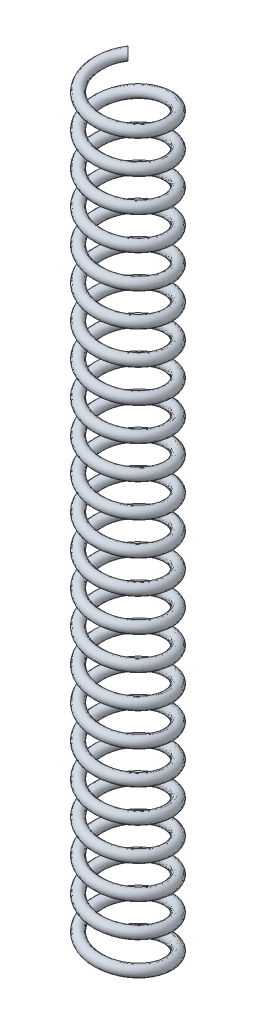
SolidWorks part; units mm, degrees
note: '?' marks a value the reader was unsure of.
ref_plane "Front Plane" through (0, 0, 0) normal (0, 0, 1) x (1, 0, 0)
ref_plane "Top Plane" through (0, 0, 0) normal (0, 1, 0) x (1, 0, 0)
ref_plane "Right Plane" through (0, 0, 0) normal (1, 0, 0) x (0, 0, -1)
sketch "Sketch1" plane through (0, 0, 0) normal (0, 1, 0) x (1, 0, 0)
  circle A0 centre (0, 0) radius 2.325
  dimension "D1" = 4.65
curve "Helix/Spiral1" pitch 2.1739 height 50 radius 2.325 left hand yes centre (0, 0, 0) axis (0, 1, 0) start towards (0, 0, 1)
ref_axis "Axis1" through (0, 52.5, 0) along (0, -1, 0)?
ref_plane "Plane1" through (0, 0, 0) normal (0.7071, 0, -0.7071) x (-0.7071, 0, -0.7071)
sketch "Sketch2" plane through (0, 0, 0) normal (0.7071, 0, -0.7071) x (-0.7071, 0, -0.7071)
  circle A0 centre (2.325, 50) radius 0.35
  spline S0 degree 3 poles (-1990.5635, 164.9826) (-222.6093, -6.3743) (13.3243, -2.7822) (1.6868, 0.2717) (0.9129, 0.4076) (0, 0.5435) (-0.9129, 0.6793) (-1.6868, 0.8152) (-2.2039, 0.9511) (-2.3855, 1.087) (-2.2039, 1.2228) (-1.6868, 1.3587) (-0.6549, 1.5399) (0.6549, 1.721) (1.6868, 1.9022) (2.2039, 2.038) (2.3855, 2.1739) (2.2039, 2.3098) (1.6868, 2.4457) (0.6549, 2.6268) (-0.6549, 2.808) (-1.6868, 2.9891) (-2.2039, 3.125) (-2.3855, 3.2609) (-2.2039, 3.3967) (-1.6868, 3.5326) (-0.6549, 3.7138) (0.6549, 3.8949) (1.6868, 4.0761) (2.2039, 4.212) (2.3855, 4.3478) (2.2039, 4.4837) (1.6868, 4.6196) (0.6549, 4.8007) (-0.6549, 4.9819) (-1.6868, 5.163) (-2.2039, 5.2989) (-2.3855, 5.4348) (-2.2039, 5.5707) (-1.6868, 5.7065) (-0.6549, 5.8877) (0.6549, 6.0688) (1.6868, 6.25) (2.2039, 6.3859) (2.3855, 6.5217) (2.2039, 6.6576) (1.6868, 6.7935) (0.6549, 6.9746) (-0.6549, 7.1558) (-1.6868, 7.337) (-2.2039, 7.4728) (-2.3855, 7.6087) (-2.2039, 7.7446) (-1.6868, 7.8804) (-0.6549, 8.0616) (0.6549, 8.2428) (1.6868, 8.4239) (2.2039, 8.5598) (2.3855, 8.6957) (2.2039, 8.8315) (1.6868, 8.9674) (0.6549, 9.1486) (-0.6549, 9.3297) (-1.6868, 9.5109) (-2.2039, 9.6467) (-2.3855, 9.7826) (-2.2039, 9.9185) (-1.6868, 10.0543) (-0.6549, 10.2355) (0.6549, 10.4167) (1.6868, 10.5978) (2.2039, 10.7337) (2.3855, 10.8696) (2.2039, 11.0054) (1.6868, 11.1413) (0.6549, 11.3225) (-0.6549, 11.5036) (-1.6868, 11.6848) (-2.2039, 11.8207) (-2.3855, 11.9565) (-2.2039, 12.0924) (-1.6868, 12.2283) (-0.6549, 12.4094) (0.6549, 12.5906) (1.6868, 12.7717) (2.2039, 12.9076) (2.3855, 13.0435) (2.2039, 13.1793) (1.6868, 13.3152) (0.6549, 13.4964) (-0.6549, 13.6775) (-1.6868, 13.8587) (-2.2039, 13.9946) (-2.3855, 14.1304) (-2.2039, 14.2663) (-1.6868, 14.4022) (-0.6549, 14.5833) (0.6549, 14.7645) (1.6868, 14.9457) (2.2039, 15.0815) (2.3855, 15.2174) (2.2039, 15.3533) (1.6868, 15.4891) (0.6549, 15.6703) (-0.6549, 15.8514) (-1.6868, 16.0326) (-2.2039, 16.1685) (-2.3855, 16.3043) (-2.2039, 16.4402) (-1.6868, 16.5761) (-0.6549, 16.7572) (0.6549, 16.9384) (1.6868, 17.1196) (2.2039, 17.2554) (2.3855, 17.3913) (2.2039, 17.5272) (1.6868, 17.663) (0.6549, 17.8442) (-0.6549, 18.0254) (-1.6868, 18.2065) (-2.2039, 18.3424) (-2.3855, 18.4783) (-2.2039, 18.6141) (-1.6868, 18.75) (-0.6549, 18.9312) (0.6549, 19.1123) (1.6868, 19.2935) (2.2039, 19.4293) (2.3855, 19.5652) (2.2039, 19.7011) (1.6868, 19.837) (0.6549, 20.0181) (-0.6549, 20.1993) (-1.6868, 20.3804) (-2.2039, 20.5163) (-2.3855, 20.6522) (-2.2039, 20.788) (-1.6868, 20.9239) (-0.6549, 21.1051) (0.6549, 21.2862) (1.6868, 21.4674) (2.2039, 21.6033) (2.3855, 21.7391) (2.2039, 21.875) (1.6868, 22.0109) (0.6549, 22.192) (-0.6549, 22.3732) (-1.6868, 22.5543) (-2.2039, 22.6902) (-2.3855, 22.8261) (-2.2039, 22.962) (-1.6868, 23.0978) (-0.6549, 23.279) (0.6549, 23.4601) (1.6868, 23.6413) (2.2039, 23.7772) (2.3855, 23.913) (2.2039, 24.0489) (1.6868, 24.1848) (0.6549, 24.3659) (-0.6549, 24.5471) (-1.6868, 24.7283) (-2.2039, 24.8641) (-2.3855, 25) (-2.2039, 25.1359) (-1.6868, 25.2717) (-0.6549, 25.4529) (0.6549, 25.6341) (1.6868, 25.8152) (2.2039, 25.9511) (2.3855, 26.087) (2.2039, 26.2228) (1.6868, 26.3587) (0.6549, 26.5399) (-0.6549, 26.721) (-1.6868, 26.9022) (-2.2039, 27.038) (-2.3855, 27.1739) (-2.2039, 27.3098) (-1.6868, 27.4457) (-0.6549, 27.6268) (0.6549, 27.808) (1.6868, 27.9891) (2.2039, 28.125) (2.3855, 28.2609) (2.2039, 28.3967) (1.6868, 28.5326) (0.6549, 28.7138) (-0.6549, 28.8949) (-1.6868, 29.0761) (-2.2039, 29.212) (-2.3855, 29.3478) (-2.2039, 29.4837) (-1.6868, 29.6196) (-0.6549, 29.8007) (0.6549, 29.9819) (1.6868, 30.163) (2.2039, 30.2989) (2.3855, 30.4348) (2.2039, 30.5707) (1.6868, 30.7065) (0.6549, 30.8877) (-0.6549, 31.0688) (-1.6868, 31.25) (-2.2039, 31.3859) (-2.3855, 31.5217) (-2.2039, 31.6576) (-1.6868, 31.7935) (-0.6549, 31.9746) (0.6549, 32.1558) (1.6868, 32.337) (2.2039, 32.4728) (2.3855, 32.6087) (2.2039, 32.7446) (1.6868, 32.8804) (0.6549, 33.0616) (-0.6549, 33.2428) (-1.6868, 33.4239) (-2.2039, 33.5598) (-2.3855, 33.6957) (-2.2039, 33.8315) (-1.6868, 33.9674) (-0.6549, 34.1486) (0.6549, 34.3297) (1.6868, 34.5109) (2.2039, 34.6467) (2.3855, 34.7826) (2.2039, 34.9185) (1.6868, 35.0543) (0.6549, 35.2355) (-0.6549, 35.4167) (-1.6868, 35.5978) (-2.2039, 35.7337) (-2.3855, 35.8696) (-2.2039, 36.0054) (-1.6868, 36.1413) (-0.6549, 36.3225) (0.6549, 36.5036) (1.6868, 36.6848) (2.2039, 36.8207) (2.3855, 36.9565) (2.2039, 37.0924) (1.6868, 37.2283) (0.6549, 37.4094) (-0.6549, 37.5906) (-1.6868, 37.7717) (-2.2039, 37.9076) (-2.3855, 38.0435) (-2.2039, 38.1793) (-1.6868, 38.3152) (-0.6549, 38.4964) (0.6549, 38.6775) (1.6868, 38.8587) (2.2039, 38.9946) (2.3855, 39.1304) (2.2039, 39.2663) (1.6868, 39.4022) (0.6549, 39.5833) (-0.6549, 39.7645) (-1.6868, 39.9457) (-2.2039, 40.0815) (-2.3855, 40.2174) (-2.2039, 40.3533) (-1.6868, 40.4891) (-0.6549, 40.6703) (0.6549, 40.8514) (1.6868, 41.0326) (2.2039, 41.1685) (2.3855, 41.3043) (2.2039, 41.4402) (1.6868, 41.5761) (0.6549, 41.7572) (-0.6549, 41.9384) (-1.6868, 42.1196) (-2.2039, 42.2554) (-2.3855, 42.3913) (-2.2039, 42.5272) (-1.6868, 42.663) (-0.6549, 42.8442) (0.6549, 43.0254) (1.6868, 43.2065) (2.2039, 43.3424) (2.3855, 43.4783) (2.2039, 43.6141) (1.6868, 43.75) (0.6549, 43.9312) (-0.6549, 44.1123) (-1.6868, 44.2935) (-2.2039, 44.4293) (-2.3855, 44.5652) (-2.2039, 44.7011) (-1.6868, 44.837) (-0.6549, 45.0181) (0.6549, 45.1993) (1.6868, 45.3804) (2.2039, 45.5163) (2.3855, 45.6522) (2.2039, 45.788) (1.6868, 45.9239) (0.6549, 46.1051) (-0.6549, 46.2862) (-1.6868, 46.4674) (-2.2039, 46.6033) (-2.3855, 46.7391) (-2.2039, 46.875) (-1.6868, 47.0109) (-0.6549, 47.192) (0.6549, 47.3732) (1.6868, 47.5543) (2.2039, 47.6902) (2.3855, 47.8261) (2.2039, 47.962) (1.6868, 48.0978) (0.6549, 48.279) (-0.6549, 48.4601) (-1.6868, 48.6413) (-2.2039, 48.7772) (-2.3855, 48.913) (-2.2039, 49.0489) (-1.6868, 49.1848) (-0.9129, 49.3207) (0, 49.4565) (0.9129, 49.5924) (1.6868, 49.7283) (13.324, 52.7821) (-222.5989, 56.3741) (-1990.4449, -114.9711) knots -0.175308 -0.175308 -0.175308 -0.175308 0.002717 0.005435 0.008152 0.01087 0.013587 0.016304 0.019022 0.021739 0.024457 0.027174 0.029891 0.035326 0.038043 0.040761 0.043478 0.046196 0.048913 0.05163 0.057065 0.059783 0.0625 0.065217 0.067935 0.070652 0.07337 0.078804 0.081522 0.084239 0.086957 0.089674 0.092391 0.095109 0.100543 0.103261 0.105978 0.108696 0.111413 0.11413 0.116848 0.122283 0.125 0.127717 0.130435 0.133152 0.13587 0.138587 0.144022 0.146739 0.149457 0.152174 0.154891 0.157609 0.160326 0.165761 0.168478 0.171196 0.173913 0.17663 0.179348 0.182065 0.1875 0.190217 0.192935 0.195652 0.19837 0.201087 0.203804 0.209239 0.211957 0.214674 0.217391 0.220109 0.222826 0.225543 0.230978 0.233696 0.236413 0.23913 0.241848 0.244565 0.247283 0.252717 0.255435 0.258152 0.26087 0.263587 0.266304 0.269022 0.274457 0.277174 0.279891 0.282609 0.285326 0.288043 0.290761 0.296196 0.298913 0.30163 0.304348 0.307065 0.309783 0.3125 0.317935 0.320652 0.32337 0.326087 0.328804 0.331522 0.334239 0.339674 0.342391 0.345109 0.347826 0.350543 0.353261 0.355978 0.361413 0.36413 0.366848 0.369565 0.372283 0.375 0.377717 0.383152 0.38587 0.388587 0.391304 0.394022 0.396739 0.399457 0.404891 0.407609 0.410326 0.413043 0.415761 0.418478 0.421196 0.42663 0.429348 0.432065 0.434783 0.4375 0.440217 0.442935 0.44837 0.451087 0.453804 0.456522 0.459239 0.461957 0.464674 0.470109 0.472826 0.475543 0.478261 0.480978 0.483696 0.486413 0.491848 0.494565 0.497283 0.5 0.502717 0.505435 0.508152 0.513587 0.516304 0.519022 0.521739 0.524457 0.527174 0.529891 0.535326 0.538043 0.540761 0.543478 0.546196 0.548913 0.55163 0.557065 0.559783 0.5625 0.565217 0.567935 0.570652 0.57337 0.578804 0.581522 0.584239 0.586957 0.589674 0.592391 0.595109 0.600543 0.603261 0.605978 0.608696 0.611413 0.61413 0.616848 0.622283 0.625 0.627717 0.630435 0.633152 0.63587 0.638587 0.644022 0.646739 0.649457 0.652174 0.654891 0.657609 0.660326 0.665761 0.668478 0.671196 0.673913 0.67663 0.679348 0.682065 0.6875 0.690217 0.692935 0.695652 0.69837 0.701087 0.703804 0.709239 0.711957 0.714674 0.717391 0.720109 0.722826 0.725543 0.730978 0.733696 0.736413 0.73913 0.741848 0.744565 0.747283 0.752717 0.755435 0.758152 0.76087 0.763587 0.766304 0.769022 0.774457 0.777174 0.779891 0.782609 0.785326 0.788043 0.790761 0.796196 0.798913 0.80163 0.804348 0.807065 0.809783 0.8125 0.817935 0.820652 0.82337 0.826087 0.828804 0.831522 0.834239 0.839674 0.842391 0.845109 0.847826 0.850543 0.853261 0.855978 0.861413 0.86413 0.866848 0.869565 0.872283 0.875 0.877717 0.883152 0.88587 0.888587 0.891304 0.894022 0.896739 0.899457 0.904891 0.907609 0.910326 0.913043 0.915761 0.918478 0.921196 0.92663 0.929348 0.932065 0.934783 0.9375 0.940217 0.942935 0.94837 0.951087 0.953804 0.956522 0.959239 0.961957 0.964674 0.970109 0.972826 0.975543 0.978261 0.980978 0.983696 0.986413 0.98913 0.991848 0.994565 0.997283 1.175304 1.175304 1.175304 1.175304 only from (2.325, 0) to (2.325, 50) construction
  spline S1 degree 3 poles (2.325, 0) (2.325, 0.045) (2.2039, 0.136) (1.6868, 0.2717) (0.9129, 0.4076) (0, 0.5435) (-0.9129, 0.6793) (-1.6868, 0.8152) (-2.2039, 0.9511) (-2.3855, 1.087) (-2.2039, 1.2228) (-1.6868, 1.3587) (-0.6549, 1.5399) (0.6549, 1.721) (1.6868, 1.9022) (2.2039, 2.038) (2.3855, 2.1739) (2.2039, 2.3098) (1.6868, 2.4457) (0.6549, 2.6268) (-0.6549, 2.808) (-1.6868, 2.9891) (-2.2039, 3.125) (-2.3855, 3.2609) (-2.2039, 3.3967) (-1.6868, 3.5326) (-0.6549, 3.7138) (0.6549, 3.8949) (1.6868, 4.0761) (2.2039, 4.212) (2.3855, 4.3478) (2.2039, 4.4837) (1.6868, 4.6196) (0.6549, 4.8007) (-0.6549, 4.9819) (-1.6868, 5.163) (-2.2039, 5.2989) (-2.3855, 5.4348) (-2.2039, 5.5707) (-1.6868, 5.7065) (-0.6549, 5.8877) (0.6549, 6.0688) (1.6868, 6.25) (2.2039, 6.3859) (2.3855, 6.5217) (2.2039, 6.6576) (1.6868, 6.7935) (0.6549, 6.9746) (-0.6549, 7.1558) (-1.6868, 7.337) (-2.2039, 7.4728) (-2.3855, 7.6087) (-2.2039, 7.7446) (-1.6868, 7.8804) (-0.6549, 8.0616) (0.6549, 8.2428) (1.6868, 8.4239) (2.2039, 8.5598) (2.3855, 8.6957) (2.2039, 8.8315) (1.6868, 8.9674) (0.6549, 9.1486) (-0.6549, 9.3297) (-1.6868, 9.5109) (-2.2039, 9.6467) (-2.3855, 9.7826) (-2.2039, 9.9185) (-1.6868, 10.0543) (-0.6549, 10.2355) (0.6549, 10.4167) (1.6868, 10.5978) (2.2039, 10.7337) (2.3855, 10.8696) (2.2039, 11.0054) (1.6868, 11.1413) (0.6549, 11.3225) (-0.6549, 11.5036) (-1.6868, 11.6848) (-2.2039, 11.8207) (-2.3855, 11.9565) (-2.2039, 12.0924) (-1.6868, 12.2283) (-0.6549, 12.4094) (0.6549, 12.5906) (1.6868, 12.7717) (2.2039, 12.9076) (2.3855, 13.0435) (2.2039, 13.1793) (1.6868, 13.3152) (0.6549, 13.4964) (-0.6549, 13.6775) (-1.6868, 13.8587) (-2.2039, 13.9946) (-2.3855, 14.1304) (-2.2039, 14.2663) (-1.6868, 14.4022) (-0.6549, 14.5833) (0.6549, 14.7645) (1.6868, 14.9457) (2.2039, 15.0815) (2.3855, 15.2174) (2.2039, 15.3533) (1.6868, 15.4891) (0.6549, 15.6703) (-0.6549, 15.8514) (-1.6868, 16.0326) (-2.2039, 16.1685) (-2.3855, 16.3043) (-2.2039, 16.4402) (-1.6868, 16.5761) (-0.6549, 16.7572) (0.6549, 16.9384) (1.6868, 17.1196) (2.2039, 17.2554) (2.3855, 17.3913) (2.2039, 17.5272) (1.6868, 17.663) (0.6549, 17.8442) (-0.6549, 18.0254) (-1.6868, 18.2065) (-2.2039, 18.3424) (-2.3855, 18.4783) (-2.2039, 18.6141) (-1.6868, 18.75) (-0.6549, 18.9312) (0.6549, 19.1123) (1.6868, 19.2935) (2.2039, 19.4293) (2.3855, 19.5652) (2.2039, 19.7011) (1.6868, 19.837) (0.6549, 20.0181) (-0.6549, 20.1993) (-1.6868, 20.3804) (-2.2039, 20.5163) (-2.3855, 20.6522) (-2.2039, 20.788) (-1.6868, 20.9239) (-0.6549, 21.1051) (0.6549, 21.2862) (1.6868, 21.4674) (2.2039, 21.6033) (2.3855, 21.7391) (2.2039, 21.875) (1.6868, 22.0109) (0.6549, 22.192) (-0.6549, 22.3732) (-1.6868, 22.5543) (-2.2039, 22.6902) (-2.3855, 22.8261) (-2.2039, 22.962) (-1.6868, 23.0978) (-0.6549, 23.279) (0.6549, 23.4601) (1.6868, 23.6413) (2.2039, 23.7772) (2.3855, 23.913) (2.2039, 24.0489) (1.6868, 24.1848) (0.6549, 24.3659) (-0.6549, 24.5471) (-1.6868, 24.7283) (-2.2039, 24.8641) (-2.3855, 25) (-2.2039, 25.1359) (-1.6868, 25.2717) (-0.6549, 25.4529) (0.6549, 25.6341) (1.6868, 25.8152) (2.2039, 25.9511) (2.3855, 26.087) (2.2039, 26.2228) (1.6868, 26.3587) (0.6549, 26.5399) (-0.6549, 26.721) (-1.6868, 26.9022) (-2.2039, 27.038) (-2.3855, 27.1739) (-2.2039, 27.3098) (-1.6868, 27.4457) (-0.6549, 27.6268) (0.6549, 27.808) (1.6868, 27.9891) (2.2039, 28.125) (2.3855, 28.2609) (2.2039, 28.3967) (1.6868, 28.5326) (0.6549, 28.7138) (-0.6549, 28.8949) (-1.6868, 29.0761) (-2.2039, 29.212) (-2.3855, 29.3478) (-2.2039, 29.4837) (-1.6868, 29.6196) (-0.6549, 29.8007) (0.6549, 29.9819) (1.6868, 30.163) (2.2039, 30.2989) (2.3855, 30.4348) (2.2039, 30.5707) (1.6868, 30.7065) (0.6549, 30.8877) (-0.6549, 31.0688) (-1.6868, 31.25) (-2.2039, 31.3859) (-2.3855, 31.5217) (-2.2039, 31.6576) (-1.6868, 31.7935) (-0.6549, 31.9746) (0.6549, 32.1558) (1.6868, 32.337) (2.2039, 32.4728) (2.3855, 32.6087) (2.2039, 32.7446) (1.6868, 32.8804) (0.6549, 33.0616) (-0.6549, 33.2428) (-1.6868, 33.4239) (-2.2039, 33.5598) (-2.3855, 33.6957) (-2.2039, 33.8315) (-1.6868, 33.9674) (-0.6549, 34.1486) (0.6549, 34.3297) (1.6868, 34.5109) (2.2039, 34.6467) (2.3855, 34.7826) (2.2039, 34.9185) (1.6868, 35.0543) (0.6549, 35.2355) (-0.6549, 35.4167) (-1.6868, 35.5978) (-2.2039, 35.7337) (-2.3855, 35.8696) (-2.2039, 36.0054) (-1.6868, 36.1413) (-0.6549, 36.3225) (0.6549, 36.5036) (1.6868, 36.6848) (2.2039, 36.8207) (2.3855, 36.9565) (2.2039, 37.0924) (1.6868, 37.2283) (0.6549, 37.4094) (-0.6549, 37.5906) (-1.6868, 37.7717) (-2.2039, 37.9076) (-2.3855, 38.0435) (-2.2039, 38.1793) (-1.6868, 38.3152) (-0.6549, 38.4964) (0.6549, 38.6775) (1.6868, 38.8587) (2.2039, 38.9946) (2.3855, 39.1304) (2.2039, 39.2663) (1.6868, 39.4022) (0.6549, 39.5833) (-0.6549, 39.7645) (-1.6868, 39.9457) (-2.2039, 40.0815) (-2.3855, 40.2174) (-2.2039, 40.3533) (-1.6868, 40.4891) (-0.6549, 40.6703) (0.6549, 40.8514) (1.6868, 41.0326) (2.2039, 41.1685) (2.3855, 41.3043) (2.2039, 41.4402) (1.6868, 41.5761) (0.6549, 41.7572) (-0.6549, 41.9384) (-1.6868, 42.1196) (-2.2039, 42.2554) (-2.3855, 42.3913) (-2.2039, 42.5272) (-1.6868, 42.663) (-0.6549, 42.8442) (0.6549, 43.0254) (1.6868, 43.2065) (2.2039, 43.3424) (2.3855, 43.4783) (2.2039, 43.6141) (1.6868, 43.75) (0.6549, 43.9312) (-0.6549, 44.1123) (-1.6868, 44.2935) (-2.2039, 44.4293) (-2.3855, 44.5652) (-2.2039, 44.7011) (-1.6868, 44.837) (-0.6549, 45.0181) (0.6549, 45.1993) (1.6868, 45.3804) (2.2039, 45.5163) (2.3855, 45.6522) (2.2039, 45.788) (1.6868, 45.9239) (0.6549, 46.1051) (-0.6549, 46.2862) (-1.6868, 46.4674) (-2.2039, 46.6033) (-2.3855, 46.7391) (-2.2039, 46.875) (-1.6868, 47.0109) (-0.6549, 47.192) (0.6549, 47.3732) (1.6868, 47.5543) (2.2039, 47.6902) (2.3855, 47.8261) (2.2039, 47.962) (1.6868, 48.0978) (0.6549, 48.279) (-0.6549, 48.4601) (-1.6868, 48.6413) (-2.2039, 48.7772) (-2.3855, 48.913) (-2.2039, 49.0489) (-1.6868, 49.1848) (-0.9129, 49.3207) (0, 49.4565) (0.9129, 49.5924) (1.6868, 49.7283) (2.2039, 49.864) (2.325, 49.955) (2.325, 50) knots 0 0 0 0 0.002717 0.005435 0.008152 0.01087 0.013587 0.016304 0.019022 0.021739 0.024457 0.027174 0.029891 0.035326 0.038043 0.040761 0.043478 0.046196 0.048913 0.05163 0.057065 0.059783 0.0625 0.065217 0.067935 0.070652 0.07337 0.078804 0.081522 0.084239 0.086957 0.089674 0.092391 0.095109 0.100543 0.103261 0.105978 0.108696 0.111413 0.11413 0.116848 0.122283 0.125 0.127717 0.130435 0.133152 0.13587 0.138587 0.144022 0.146739 0.149457 0.152174 0.154891 0.157609 0.160326 0.165761 0.168478 0.171196 0.173913 0.17663 0.179348 0.182065 0.1875 0.190217 0.192935 0.195652 0.19837 0.201087 0.203804 0.209239 0.211957 0.214674 0.217391 0.220109 0.222826 0.225543 0.230978 0.233696 0.236413 0.23913 0.241848 0.244565 0.247283 0.252717 0.255435 0.258152 0.26087 0.263587 0.266304 0.269022 0.274457 0.277174 0.279891 0.282609 0.285326 0.288043 0.290761 0.296196 0.298913 0.30163 0.304348 0.307065 0.309783 0.3125 0.317935 0.320652 0.32337 0.326087 0.328804 0.331522 0.334239 0.339674 0.342391 0.345109 0.347826 0.350543 0.353261 0.355978 0.361413 0.36413 0.366848 0.369565 0.372283 0.375 0.377717 0.383152 0.38587 0.388587 0.391304 0.394022 0.396739 0.399457 0.404891 0.407609 0.410326 0.413043 0.415761 0.418478 0.421196 0.42663 0.429348 0.432065 0.434783 0.4375 0.440217 0.442935 0.44837 0.451087 0.453804 0.456522 0.459239 0.461957 0.464674 0.470109 0.472826 0.475543 0.478261 0.480978 0.483696 0.486413 0.491848 0.494565 0.497283 0.5 0.502717 0.505435 0.508152 0.513587 0.516304 0.519022 0.521739 0.524457 0.527174 0.529891 0.535326 0.538043 0.540761 0.543478 0.546196 0.548913 0.55163 0.557065 0.559783 0.5625 0.565217 0.567935 0.570652 0.57337 0.578804 0.581522 0.584239 0.586957 0.589674 0.592391 0.595109 0.600543 0.603261 0.605978 0.608696 0.611413 0.61413 0.616848 0.622283 0.625 0.627717 0.630435 0.633152 0.63587 0.638587 0.644022 0.646739 0.649457 0.652174 0.654891 0.657609 0.660326 0.665761 0.668478 0.671196 0.673913 0.67663 0.679348 0.682065 0.6875 0.690217 0.692935 0.695652 0.69837 0.701087 0.703804 0.709239 0.711957 0.714674 0.717391 0.720109 0.722826 0.725543 0.730978 0.733696 0.736413 0.73913 0.741848 0.744565 0.747283 0.752717 0.755435 0.758152 0.76087 0.763587 0.766304 0.769022 0.774457 0.777174 0.779891 0.782609 0.785326 0.788043 0.790761 0.796196 0.798913 0.80163 0.804348 0.807065 0.809783 0.8125 0.817935 0.820652 0.82337 0.826087 0.828804 0.831522 0.834239 0.839674 0.842391 0.845109 0.847826 0.850543 0.853261 0.855978 0.861413 0.86413 0.866848 0.869565 0.872283 0.875 0.877717 0.883152 0.88587 0.888587 0.891304 0.894022 0.896739 0.899457 0.904891 0.907609 0.910326 0.913043 0.915761 0.918478 0.921196 0.92663 0.929348 0.932065 0.934783 0.9375 0.940217 0.942935 0.94837 0.951087 0.953804 0.956522 0.959239 0.961957 0.964674 0.970109 0.972826 0.975543 0.978261 0.980978 0.983696 0.986413 0.98913 0.991848 0.994565 0.997283 1 1 1 1 construction
  point P2 (3.4645, 70.9823)
  point P3 (3.2181, 51.1045)
  point P4 (0, 0)
  point P7 (0, 0)
  dimension "D1" = 0.7
sweep "Sweep1" add profiles "Sketch2" path "Helix/Spiral1"
